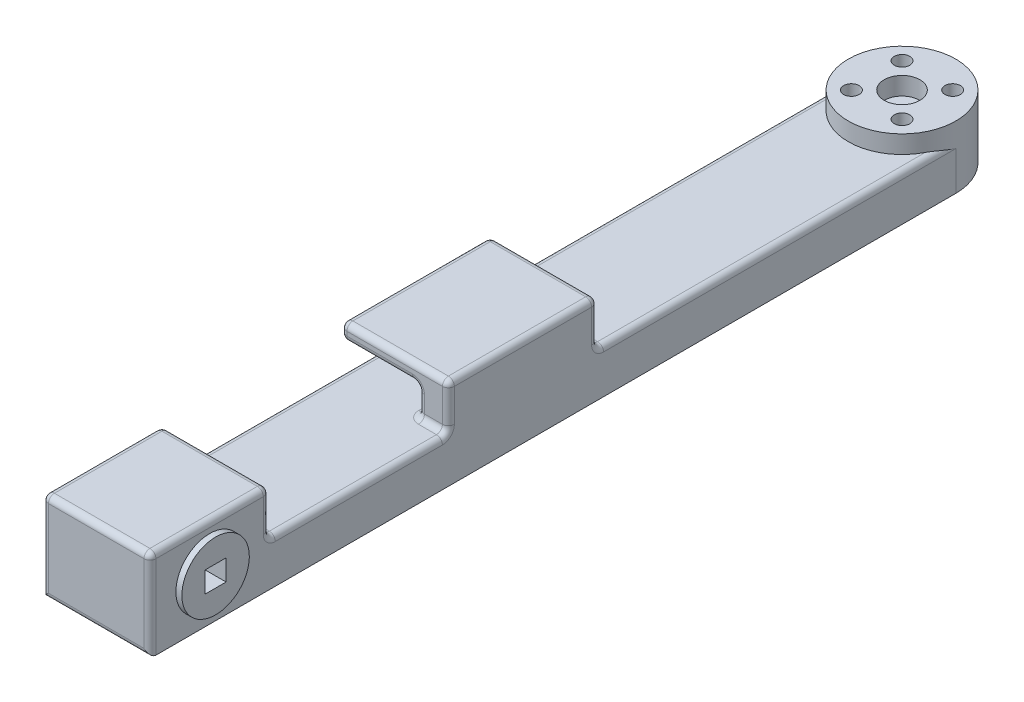
SolidWorks part; units mm, degrees
ref_plane "Front Plane" through (0, 0, 0) normal (0, 0, 1) x (1, 0, 0)
ref_plane "Top Plane" through (0, 0, 0) normal (0, 1, 0) x (1, 0, 0)
ref_plane "Right Plane" through (0, 0, 0) normal (1, 0, 0) x (0, 0, -1)
sketch "Sketch1" plane through (0, 0, 0) normal (0, 0, 1) x (1, 0, 0)
  line L1 (0, 0) -> (18, 0)
  line L2 (0, 0) -> (0, 15)
  line L3 (0, 15) -> (18, 15)
  line L4 (18, 0) -> (18, 15)
  dimension "D1" = 18
  dimension "D2" = 15
extrude "Boss-Extrude1" add sketch "Sketch1" along normal blind 40 and the other way blind 125
sketch "Sketch2" plane through (18, 0, 0) normal (1, 0, 0) x (0, 0, -1)
  line L0 (0, 0) -> (0, 15) construction
  line L1 (125, 15) -> (-40, 15) construction
  circle A0 centre (0, 7.5) radius 5.65
  dimension "D1" = 11.3
extrude "Boss-Extrude2" add sketch "Sketch2" along normal blind 1 contours A0
ref_plane "Plane1" through (9, 0, 0) normal (1, 0, 0) x (0, 0, -1)
mirror "Mirror1" about plane through (9, 0, 0) normal (1, 0, 0) of "Boss-Extrude2"
sketch "Sketch3" plane through (19, 0, 0) normal (1, 0, 0) x (0, 0, -1)
  line L1 (-1.755, 5.745) -> (1.755, 5.745)
  line L2 (-1.755, 5.745) -> (-1.755, 9.255)
  line L3 (-1.755, 9.255) -> (1.755, 9.255)
  line L4 (1.755, 5.745) -> (1.755, 9.255)
  line L5 (-1.755, 5.745) -> (1.755, 9.255) construction
  line L6 (-1.755, 9.255) -> (1.755, 5.745) construction
  point P0 (0, 7.5)
  dimension "D1" = 3.51
  dimension "D2" = 3.51
extrude "Cut-Extrude1" cut sketch "Sketch3" against normal up to next
sketch "Sketch4" plane through (18, 0, 0) normal (1, 0, 0) x (0, 0, -1)
  line L1 (125, 15) -> (10, 15)
  line L2 (125, 15) -> (125, 7.5)
  line L3 (125, 7.5) -> (10, 7.5)
  line L4 (10, 15) -> (10, 7.5)
  line L5 (-40, 15) -> (-10, 15)
  line L6 (-40, 15) -> (-40, 0)
  line L7 (-40, 0) -> (-10, 0)
  line L8 (-10, 15) -> (-10, 0)
  dimension "D1" = 115
  dimension "D2" = 7.5
  dimension "D3" = 30
  dimension "D4" = 15
extrude "Cut-Extrude2" cut sketch "Sketch4" against normal up to next
sketch "Sketch6" plane through (0, 7.5, 0) normal (0, 1, 0) x (1, 0, 0)
  line L0 (0, 125) -> (18, 125) construction
  circle A0 centre (9, 125) radius 9
extrude "Boss-Extrude4" add sketch "Sketch6" along normal blind 3 and the other way blind 7.5
sketch "Sketch9" plane through (0, 10.5, 0) normal (0, 1, 0) x (1, 0, 0)
  line L0 (9, 125) -> (9, 131) construction
  line L1 (9, 125) -> (13.2426, 129.2426) construction
  line L2 (18, 125) -> (0, 125) construction
  circle A0 centre (9, 125) radius 3
  circle A1 centre (13.2426, 129.2426) radius 1.3
  circle A5 centre (9, 125) radius 9 construction
  circle A6 centre (13.2426, 120.7574) radius 1.3
  circle A7 centre (4.7574, 120.7574) radius 1.3
  circle A8 centre (4.7574, 129.2426) radius 1.3
  point P19 (9, 125)
  dimension "D1" = 6
  dimension "D5" = 2.6
  dimension "D2" = 6
  dimension "D3" = 45
  dimension "D4" = 6
  dimension "D6" = 4
extrude "Cut-Extrude3" cut sketch "Sketch9" against normal blind 3
sketch "Sketch10" plane through (0, 0, 0) normal (0, -1, 0) x (1, 0, 0)
  line L0 (9, -125) -> (9, -131) construction
  line L1 (9, -125) -> (4.7574, -129.2426) construction
  line L2 (18, -125) -> (0, -125) construction
  circle A0 centre (4.7574, -129.2426) radius 2.4
  circle A4 centre (4.7574, -120.7574) radius 2.4
  circle A5 centre (13.2426, -120.7574) radius 2.4
  circle A6 centre (13.2426, -129.2426) radius 2.4
  point P16 (9, -125)
  dimension "D4" = 4.8
  dimension "D1" = 6
  dimension "D2" = 6
  dimension "D3" = 45
  dimension "D5" = 4
extrude "Cut-Extrude4" cut sketch "Sketch10" against normal blind 7.5
sketch "Sketch13" plane through (18, 0, 0) normal (1, 0, 0) x (0, 0, -1)
  line L0 (10, 7.5) -> (40, 7.5) construction
  line L1 (10, 7.5) -> (125, 7.5) construction
  line L2 (40, 7.5) -> (65, 7.5)
  line L5 (40, 7.5) -> (40, 15)
  line L6 (40, 15) -> (65, 15)
  line L7 (65, 7.5) -> (65, 15)
  dimension "D1" = 30
  dimension "D2" = 25
  dimension "D3" = 7.5
extrude "Boss-Extrude5" add sketch "Sketch13" against normal blind 5
sketch "Sketch14" plane through (13, 0, 0) normal (-1, 0, 0) x (0, 0, 1)
  line L0 (-40, 15) -> (-40, 7.5) construction
  line L1 (-65, 15) -> (-40, 15)
  line L2 (-65, 15) -> (-65, 12.3)
  line L3 (-65, 12.3) -> (-40, 12.3)
  line L4 (-40, 15) -> (-40, 12.3)
  dimension "D1" = 2.7
extrude "Boss-Extrude6" add sketch "Sketch14" along normal blind 13
fillet "Fillet3" radius 1 30 edges at (18, 15, 0) (9, 15, 10) (0, 15, 0) (9, 15, -10) (18, 7.5, -95) (0, 7.5, -67.5) (18, 7.5, -25) (13, 7.5, -52.5) (13, 12.3, -52.5) (0, 12.3, -52.5) (0, 13.65, -65) (6.5, 12.3, -65) (13, 9.9, -65) (15.5, 7.5, -65) (18, 11.25, -65) (0, 15, -52.5) (9, 15, -65) (18, 15, -52.5) (15.5, 7.5, -40) (13, 9.9, -40) (6.5, 12.3, -40) (0, 13.65, -40) (9, 15, -40) (18, 11.25, -40) (0, 7.5, 10) (18, 7.5, 10) (9, 0, 10) (0, 11.25, -10) (9, 7.5, -10) (18, 11.25, -10)
